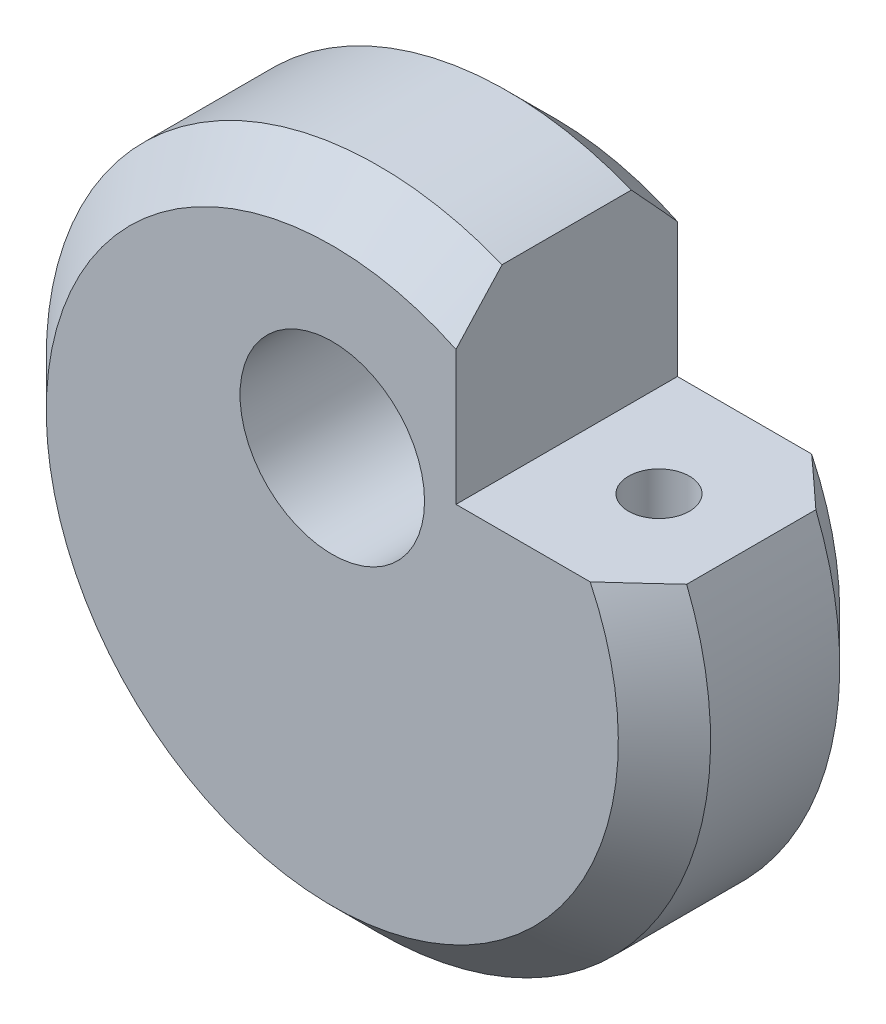
SolidWorks part; units mm, degrees
ref_plane "Front Plane" through (0, 0, 0) normal (0, 0, 1) x (1, 0, 0)
ref_plane "Top Plane" through (0, 0, 0) normal (0, 1, 0) x (1, 0, 0)
ref_plane "Right Plane" through (0, 0, 0) normal (1, 0, 0) x (0, 0, -1)
sketch "Sketch1" plane through (0, 0, 0) normal (0, 0, 1) x (1, 0, 0)
  line L0 (-18, 0) -> (18, 0) construction
  line L1 (0, 18) -> (0, -18) construction
  line L3 (16.7047, 6.7047) -> (6.7047, 6.7047)
  line L4 (6.7047, 6.7047) -> (6.7047, 16.7047)
  circle A0 centre (0, 0) radius 18
  circle A1 centre (0, 6) radius 5
  arc A2 (6.7047, 16.7047) -> (16.7047, 6.7047) centre (0, 0) cw
  dimension "D1" = 36
  dimension "D3" = 10
  dimension "D2" = 6
  dimension "D4" = 10
  dimension "D5" = 10
extrude "Boss-Extrude1" add sketch "Sketch1" against normal blind 12 contours A0
sketch "Sketch2" plane through (0, 0, 0) normal (0, 0, 1) x (1, 0, 0)
  arc A0 (6.7047, 16.7047) -> (16.7047, 6.7047) centre (0, 0) cw
extrude "Cut-Extrude4" cut sketch "Sketch1<4>" against normal blind 17 contours L4 A2 L3
sketch "Sketch1<4>" plane through (0, 0, 0) normal (0, 0, 1) x (1, 0, 0) same geometry as "Sketch1"
extrude "Cut-Extrude5" cut sketch "Sketch1<5>" against normal blind 22 contours A1
sketch "Sketch1<5>" plane through (0, 0, 0) normal (0, 0, 1) x (1, 0, 0) same geometry as "Sketch1"
sketch "Sketch4" plane through (0, 6.7047, 0) normal (0, 1, 0) x (1, 0, 0)
  line L0 (6.7047, 6) -> (11.7047, 6)
  line L1 (6.7047, 12) -> (6.7047, 0) construction
  line L2 (11.7047, 6) -> (11.7047, 12)
  line L3 (16.7047, 12) -> (6.7047, 12) construction
  point P9 (11.7047, 6)
  point P10 (11.7047, 6)
  dimension "D1" = 5
  dimension "D2" = 6
hole_wizard "M4 Tapped Hole1" positions "Sketch11" profile "Sketch12" tap size "M4" standard "ISO"
sketch "Sketch11" plane through (0, 6.7047, 0) normal (0, 1, 0) x (1, 0, 0)
  point P0 (11.7047, 6)
sketch "Sketch12" plane through (11.7047, 6.7047, -6) normal (1, 0, 0) x (0, 0, 1)
  line L0 (0, 0) -> (0, 14.9914)
  line L1 (0, 14.9914) -> (1.65, 14)
  line L2 (1.65, 14) -> (1.65, 0)
  line L5 (1.65, 0) -> (0, 0)
  line L10 (0, 14.9914) -> (-1.65, 14) construction
  line L11 (0, -6.35) -> (0, 107.95) construction
  dimension "Tap Drill Dia." = 3.3
  dimension "Tap Drill Depth" = 14
  dimension "Drill Angle" = 118
cosmetic thread "Hole Thread1" parameters "D1"=10, "D2"=4
chamfer "Chamfer1" distance 2.5 angle 45 1 edges at (-12.7279, -12.7279, 0)
chamfer "Chamfer2" distance 2.5 angle 45 1 edges at (-12.7279, -12.7279, -12)
